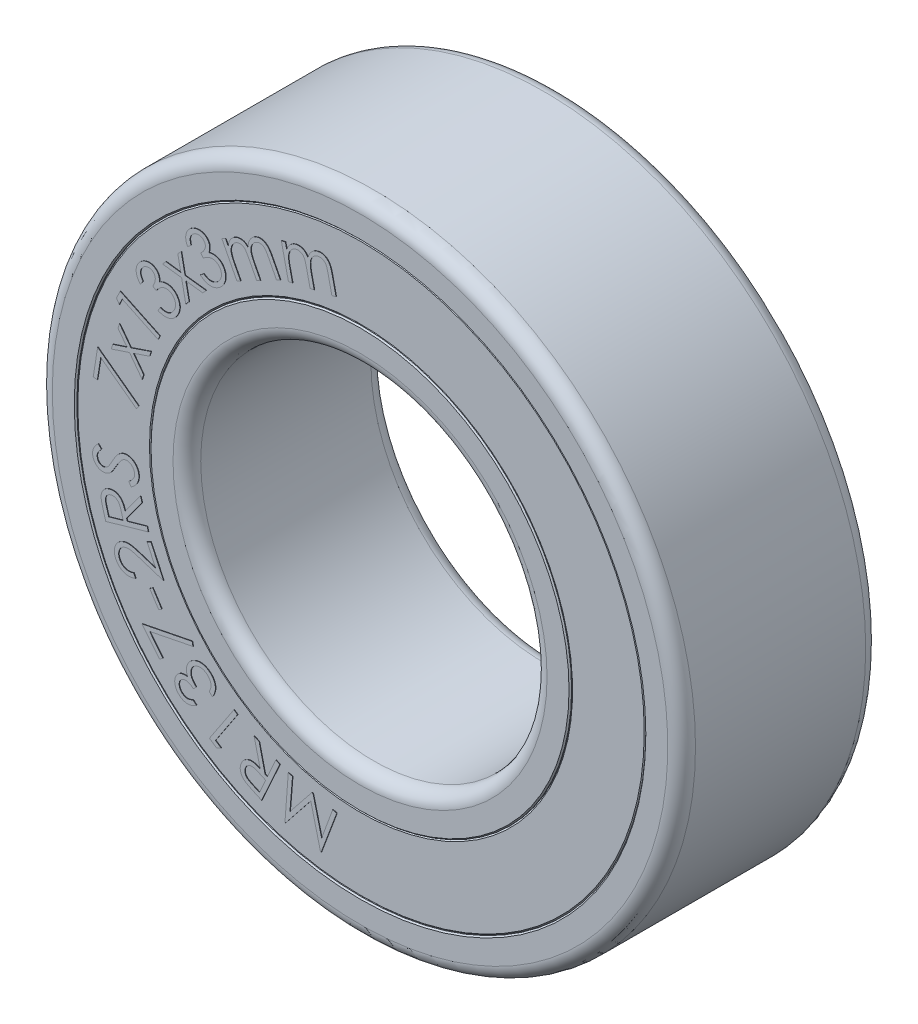
SolidWorks part; units mm, degrees
material "AISI 316 Annealed Stainless Steel Bar (SS)"
ref_plane "Front" through (0, 0, 0) normal (0, 0, 1) x (1, 0, 0)
ref_plane "Top" through (0, 0, 0) normal (0, 1, 0) x (1, 0, 0)
ref_plane "Right" through (0, 0, 0) normal (1, 0, 0) x (0, 0, -1)
sketch "LAYOUT R" plane through (0, 0, 0) normal (1, 0, 0) x (0, 0, -1)
  line L0 (-2, 3.5) -> (2, 3.5)
  line L1 (2, -6.5) -> (-2, -6.5) construction
  line L2 (2, -6.5) -> (2, 6.5) construction
  line L3 (2, 6.5) -> (-2, 6.5)
  line L4 (-2, -6.5) -> (-2, 6.5) construction
  line L5 (2, -6.5) -> (-2, 6.5) construction
  line L6 (2, 6.5) -> (-2, -6.5) construction
  line L7 (-2, 4.25) -> (2, 4.25)
  line L8 (-2, 5.75) -> (2, 5.75)
  line L11 (-17.5, 0) -> (17.5, 0) construction
  line L12 (-2, 6.5) -> (-2, 5.75)
  line L13 (2, 6.5) -> (2, 5.75)
  line L14 (-2, 5.75) -> (-2, 4.25)
  line L15 (2, 5.75) -> (2, 4.25)
  line L16 (-2, 4.25) -> (-2, 3.5)
  line L17 (2, 4.25) -> (2, 3.5)
  line L18 (-1.98, 5.75) -> (-1.98, 4.25)
  line L19 (1.98, 5.75) -> (1.98, 4.25)
  point P0 (0, 0)
  point P15 (0, 0)
  dimension "D1" = 4
  dimension "D2" = 13
  dimension "D3" = 3.5
  dimension "D6" = 0.02
  dimension "D7" = 0.02
  dimension "D4" = 4.25
  dimension "D5" = 5.75
sketch "Sketch R, INNER BODY" plane through (0, 0, 0) normal (1, 0, 0) x (0, 0, -1)
  line L0 (-2, 3.5) -> (2, 3.5) construction
  line L2 (-2, 4.25) -> (2, 4.25) construction
  line L4 (-2, 3.5) -> (2, 3.5)
  line L6 (-2, 4.25) -> (2, 4.25)
  line L8 (2, 4.25) -> (2, 3.5) construction
  line L9 (-2, 4.25) -> (-2, 3.5) construction
  line L10 (2, 4.25) -> (2, 3.5)
  line L11 (-2, 4.25) -> (-2, 3.5)
  line L12 (-17.5, 0) -> (17.5, 0) construction
  line L13 (-17.5, 0) -> (17.5, 0) construction
sketch "Sketch R, OUTER BODY" plane through (0, 0, 0) normal (1, 0, 0) x (0, 0, -1)
  line L2 (-2, 5.75) -> (2, 5.75) construction
  line L3 (2, 6.5) -> (-2, 6.5) construction
  line L6 (-2, 5.75) -> (2, 5.75)
  line L7 (2, 6.5) -> (-2, 6.5)
  line L8 (-17.5, 0) -> (17.5, 0) construction
  line L9 (-17.5, 0) -> (17.5, 0) construction
  line L10 (2, 6.5) -> (2, 5.75) construction
  line L11 (-2, 6.5) -> (-2, 5.75) construction
  line L12 (2, 6.5) -> (2, 5.75)
  line L13 (-2, 6.5) -> (-2, 5.75)
sketch "Sketch R, SEAL FACES" plane through (0, 0, 0) normal (1, 0, 0) x (0, 0, -1)
  line L0 (-17.5, 0) -> (17.5, 0) construction
  line L1 (-17.5, 0) -> (17.5, 0) construction
  line L3 (-2, 4.25) -> (2, 4.25) construction
  line L5 (-2, 5.75) -> (2, 5.75) construction
  line L7 (-1.98, 4.25) -> (1.98, 4.25)
  line L9 (-1.98, 5.75) -> (1.98, 5.75)
  line L10 (1.98, 5.75) -> (1.98, 4.25) construction
  line L11 (-1.98, 5.75) -> (-1.98, 4.25) construction
  line L12 (1.98, 5.75) -> (1.98, 4.25)
  line L13 (-1.98, 5.75) -> (-1.98, 4.25)
revolve "Revolve INNER BODY" add sketch "Sketch R, INNER BODY" angle 360 about L13
fillet "Fillet INNER BODY" radius 0.28 2 edges at (3.5, 0, 2) (3.5, 0, -2)
chamfer "Chamfer INNER BODY" distance 0.026 angle 45 2 edges at (4.25, 0, -2) (4.25, 0, 2)
revolve "Revolve OUTER BODY" add sketch "Sketch R, OUTER BODY" angle 360 about L9
fillet "Fillet OUTER BODY" radius 0.28 2 edges at (6.5, 0, -2) (6.5, 0, 2)
chamfer "Chamfer OUTER BODY" distance 0.026 angle 45 2 edges at (5.75, 0, 2) (5.75, 0, -2)
revolve "Revolve SEALS" add sketch "Sketch R, SEAL FACES" angle 360 about L1
chamfer "Chamfer SEALS" distance 0.026 angle 45 4 edges at (4.25, 0, -1.98) (5.75, 0, -1.98) (5.75, 0, 1.98) (4.25, 0, 1.98)
sketch "Sketch TEXT RADIUS 1 — MANUALLY ASSIGN TEXT AND FONT SIZE (FROM EQUATIONS)" plane through (0, 0, 1.98) normal (0, 0, 1) x (1, 0, 0)
  circle A0 centre (0, 0) radius 4.55 construction
  text T0 "MR137-2RS  7x13x3mm" font "Century Gothic" height 0.9
  dimension "D1" = 9.1
extrude "Boss-Extrude SEAL LABEL 1" add sketch "Sketch TEXT RADIUS 1 — MANUALLY ASSIGN TEXT AND FONT SIZE (FROM EQUATIONS)" along normal blind 0.01
sketch "Sketch TEXT RADIUS 2 — MANUALLY ASSIGN TEXT AND FONT SIZE (FROM EQUATIONS)" plane through (0, 0, -1.98) normal (0, 0, -1) x (-1, 0, 0)
  circle A0 centre (0, 0) radius 4.55 construction
  text T0 "MR137-2RS  7x13x3mm" font "Century Gothic" height 0.9
  dimension "D1" = 9.1
extrude "Boss-Extrude SEAL LABEL 2" add sketch "Sketch TEXT RADIUS 2 — MANUALLY ASSIGN TEXT AND FONT SIZE (FROM EQUATIONS)" along normal blind 0.01
equation "\"_i__BORE\"= 7"
equation "\"_i__OUTSIDE_DIAMETER\"= 13"
equation "\"_i__WIDTH\"= 4"
equation "\"__user_applied_FONT_SIZE\"= \"BODY_SPAN__SEAL__OF_RADIUS\" * \"param__FONT_SIZE_RATIO\"'MANUALLY ASSIGN TO FONT"
equation "\"BODY__HALF_WIDTH\"= \"_i__WIDTH\" / 2"
equation "\"BODY_SPAN___OF_DIAMETER\"= \"_i__OUTSIDE_DIAMETER\" - \"_i__BORE\""
equation "\"BODY_SPAN___OF_RADIUS\"= \"BODY_SPAN___OF_DIAMETER\" / 2"
equation "\"BODY_SPAN__BORE_AND_OD__OF RADIUS\"= ( \"BODY_SPAN___OF_RADIUS\" - \"BODY_SPAN__SEAL__OF_RADIUS\" ) / 2"
equation "\"BODY_SPAN__SEAL__OF_RADIUS\"= \"BODY_SPAN___OF_RADIUS\" * \"param__SEAL_PANEL_SPAN__RATIO_OF_BODY_RADIAN\""
equation "\"BORE__RADIUS\"= \"_i__BORE\" / 2"
equation "\"CORNER_RADII\"= \"_i__WIDTH\" * \"param__CORNER_RADII__ISO_MAX_RATIO_TO_WIDTH\""
equation "\"RING_INNER__OUTSIDE_RADIUS\"= \"BORE__RADIUS\" + \"BODY_SPAN__BORE_AND_OD__OF RADIUS\""
equation "\"RING_OUTER__OUTSIDE_RADIUS\"= ( \"_i__OUTSIDE_DIAMETER\" / 2 ) - \"BODY_SPAN__BORE_AND_OD__OF RADIUS\""
equation "\"SEAL_FACE_INSET\"= \"_i__WIDTH\" * \"param__SEAL_FACE_INSET__RATIO_OF_WIDTH\""
equation "\"SIDE_FACE_AND_SEAL_CHAMFERS\"= \"_i__OUTSIDE_DIAMETER\" * \"param__SIDE_CHAMFERS__RATIO_TO_OD\""
equation "\"TEXT_RADIUS\"= \"_i__BORE\" + ( \"BODY_SPAN___OF_DIAMETER\" / 2 ) - \"__user_applied_FONT_SIZE\""
equation "\"D1@Chamfer INNER BODY\"=\"SIDE_FACE_AND_SEAL_CHAMFERS\""
equation "\"D1@Chamfer OUTER BODY\"=\"SIDE_FACE_AND_SEAL_CHAMFERS\""
equation "\"D1@Chamfer SEALS\"=\"SIDE_FACE_AND_SEAL_CHAMFERS\""
equation "\"D1@Fillet INNER BODY\"=\"CORNER_RADII\""
equation "\"D1@Fillet OUTER BODY\"=\"CORNER_RADII\""
equation "\"D1@LAYOUT R\"=\"_i__WIDTH\""
equation "\"D1@Sketch TEXT RADIUS 1 — MANUALLY ASSIGN TEXT AND FONT SIZE (FROM EQUATIONS)\" = \"TEXT_RADIUS\""
equation "\"D1@Sketch TEXT RADIUS 2 — MANUALLY ASSIGN TEXT AND FONT SIZE (FROM EQUATIONS)\" = \"TEXT_RADIUS\""
equation "\"D2@LAYOUT R\"=\"_i__OUTSIDE_DIAMETER\""
equation "\"D3@LAYOUT R\"=\"BORE__RADIUS\""
equation "\"D4@LAYOUT R\"=\"RING_INNER__OUTSIDE_RADIUS\""
equation "\"D5@LAYOUT R\"=\"RING_OUTER__OUTSIDE_RADIUS\""
equation "\"param__CORNER_RADII__ISO_MAX_RATIO_TO_WIDTH\"= 0.07'ISO STANDARD WHERE WIDTH IS LESS THAN DIAMETER"
equation "\"param__FONT_SIZE_RATIO\"= 0.6'EXPRESSES RADIAL PROPORTION OF SEAL FACE, ORIGINAL PRE-20240212 VALUE WAS 0.3"
equation "\"param__INDICIA__EXTRUSION_HEIGHT\"=0.01'RAISED INDICIA ON SEAL FACES"
equation "\"param__SEAL_FACE_INSET__RATIO_OF_WIDTH\"= 0.01'ISO-UNSPECIFIED"
equation "\"param__SEAL_PANEL_SPAN__RATIO_OF_BODY_RADIAN\"= 0.5'ISO-UNSPECIFIED"
equation "\"param__SIDE_CHAMFERS__RATIO_TO_OD\"= 0.002'1/500, ISO-UNSPECIFIED"
equation "\"D1@Boss-Extrude SEAL LABEL 1\" = \"param__INDICIA__EXTRUSION_HEIGHT\""
equation "\"D1@Boss-Extrude SEAL LABEL 2\" = \"param__INDICIA__EXTRUSION_HEIGHT\""
